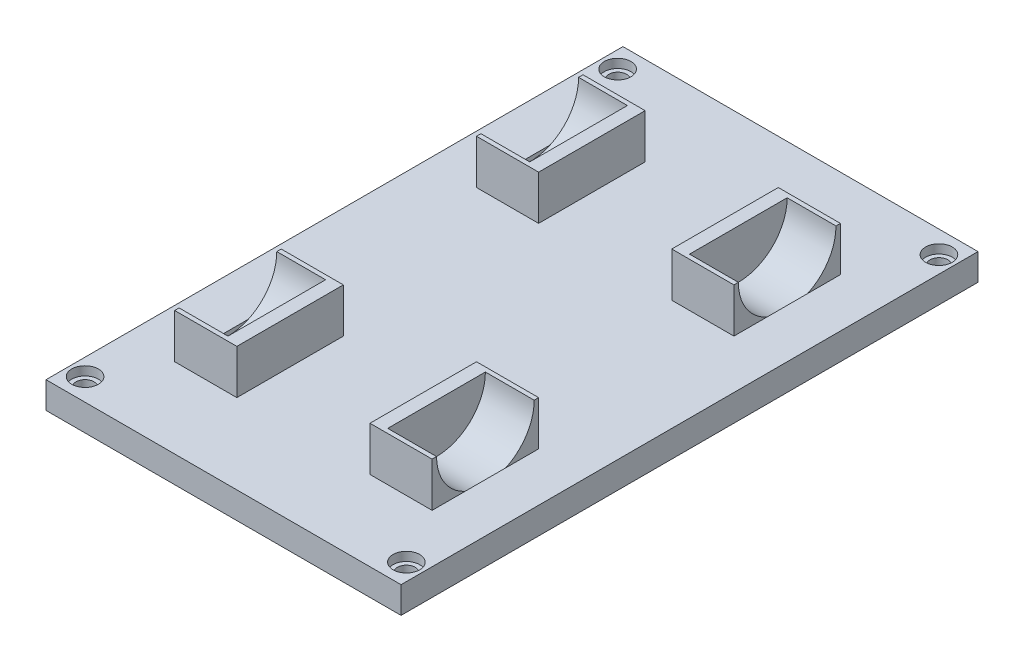
SolidWorks part; units mm, degrees
other "标注1"
sketch "草图3" plane through (-22.25, 4, -10) normal (-0.231, 0.6469, -0.7268) x (-0.9696, -0.2151, 0.1167)
ref_plane "前视基准面" through (0, 0, 0) normal (0, 0, 1) x (1, 0, 0)
ref_plane "上视基准面" through (0, 0, 0) normal (0, 1, 0) x (1, 0, 0)
ref_plane "右视基准面" through (0, 0, 0) normal (1, 0, 0) x (0, 0, -1)
other "Configuration Table"
sketch "草图4" plane through (0, 0, 0) normal (0, 1, 0) x (1, 0, 0)
  line L1 (-20, -32.5) -> (20, -32.5)
  line L2 (-20, -32.5) -> (-20, 32.5)
  line L3 (-20, 32.5) -> (20, 32.5)
  line L4 (20, -32.5) -> (20, 32.5)
  line L5 (-20, -32.5) -> (20, 32.5) construction
  line L6 (-20, 32.5) -> (20, -32.5) construction
  point P0 (0, 0)
  dimension "D1" = 40
  dimension "D2" = 65
extrude "凸台-拉伸1" add sketch "草图4" along normal blind 3 contours L1 L4 L3 L2
sketch "草图5" plane through (0, 0, 0) normal (0, -1, 0) x (1, 0, 0)
  line L0 (0, 22.5) -> (0, -22.5) construction
  line L1 (-12, 22.5) -> (12, 22.5) construction
  line L2 (-12, 22.5) -> (-12, -22.5) construction
  line L3 (-12, -22.5) -> (12, -22.5) construction
  line L4 (12, 22.5) -> (12, -22.5) construction
  circle A0 centre (-12, 22.5) radius 5.05
  circle A1 centre (12, 22.5) radius 5.05
  circle A2 centre (12, -22.5) radius 5.05
  circle A4 centre (-12, -22.5) radius 5.05
  point P13 (-3.9138, -14.8211)
  point P14 (40.4715, -21.1778)
  point P16 (40.1927, 20.308)
  dimension "D1" = 10.1
  dimension "D2" = 24
  dimension "D3" = 45
extrude "切除-拉伸1" cut sketch "草图5" against normal blind 2
sketch "草图6" plane through (0, 3, 0) normal (0, 1, 0) x (1, 0, 0)
  line L0 (0, -30) -> (0, 30) construction
  line L1 (-18.1, -30) -> (18.1, -30) construction
  line L2 (-18.1, -30) -> (-18.1, 30) construction
  line L3 (-18.1, 30) -> (18.1, 30) construction
  line L4 (18.1, -30) -> (18.1, 30) construction
  circle A0 centre (-18.1, 30) radius 1.5
  circle A1 centre (18.1, 30) radius 1.5
  circle A2 centre (-18.1, -30) radius 1.5
  circle A3 centre (18.1, -30) radius 1.5
  circle A4 centre (-18.1, -30) radius 1
  circle A5 centre (18.1, -30) radius 1
  circle A6 centre (18.1, 30) radius 1
  circle A7 centre (-18.1, 30) radius 1
  dimension "D1" = 3
  dimension "D2" = 2
  dimension "D3" = 36.2
  dimension "D4" = 60
extrude "切除-拉伸2" cut sketch "草图6" against normal blind 1
extrude "切除-拉伸3" cut sketch "草图6<2>" against normal through all contours A6 | A7 | A5 | A4
sketch "草图6<2>" plane through (0, 3, 0) normal (0, 1, 0) x (1, 0, 0) same geometry as "草图6"
sketch "草图7" plane through (0, 3, 0) normal (0, 1, 0) x (1, 0, 0)
  line L1 (-14.5, 22.5) -> (-7.5, 22.5)
  line L2 (-14.5, 22.5) -> (-14.5, 10.5)
  line L3 (-14.5, 10.5) -> (-7.5, 10.5)
  line L4 (-7.5, 22.5) -> (-7.5, 10.5)
  line L5 (14.5, 22.5) -> (7.5, 22.5)
  line L6 (14.5, 22.5) -> (14.5, 10.5)
  line L7 (14.5, 10.5) -> (7.5, 10.5)
  line L8 (7.5, 22.5) -> (7.5, 10.5)
  line L9 (14.5, -11.5) -> (7.5, -11.5)
  line L10 (14.5, -11.5) -> (14.5, -23.5)
  line L11 (14.5, -23.5) -> (7.5, -23.5)
  line L12 (7.5, -11.5) -> (7.5, -23.5)
  line L13 (-14.5, -23.5) -> (-7.5, -23.5)
  line L14 (-14.5, -23.5) -> (-14.5, -11.5)
  line L15 (-14.5, -11.5) -> (-7.5, -11.5)
  line L16 (-7.5, -23.5) -> (-7.5, -11.5)
  line L18 (-7.5, 16.5) -> (7.5, 16.5) construction
  line L23 (-7.5, -17.5) -> (7.5, -17.5) construction
  line L24 (0, 16.5) -> (0, -17.5) construction
  line L25 (-20, 32.5) -> (20, 32.5) construction
  point P25 (0, 32.5)
  dimension "D1" = 34
  dimension "D2" = 7
  dimension "D3" = 15
  dimension "D4" = 12
  dimension "D5" = 16
extrude "凸台-拉伸2" add sketch "草图7" along normal blind 5
sketch "草图8" plane through (-14.5, 0, 0) normal (-1, 0, 0) x (0, 0, 1)
  line L0 (-22.5, 8) -> (-10.5, 8) construction
  line L1 (11.5, 8) -> (23.5, 8) construction
  circle A0 centre (-16.5, 8) radius 5.5
  circle A1 centre (17.5, 8) radius 5.5
  dimension "D1" = 11
extrude "切除-拉伸4" cut sketch "草图8" against normal blind 5.5
extrude "切除-拉伸5" cut sketch "草图8<2>" along normal blind 5.5 from surface starting at face at (14.5, 5.5, 17.5)
sketch "草图8<2>" plane through (-14.5, 0, 0) normal (-1, 0, 0) x (0, 0, 1) same geometry as "草图8"
